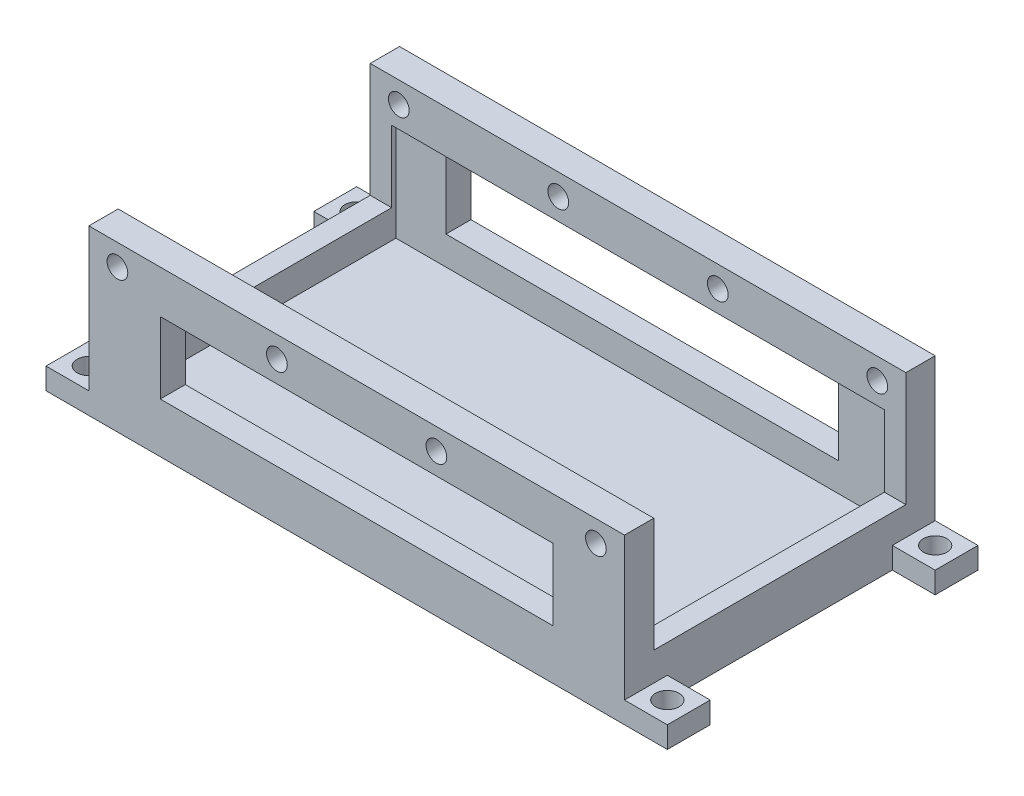
SolidWorks part; units mm, degrees
ref_plane "Front Plane" through (0, 0, 0) normal (0, 0, 1) x (1, 0, 0)
ref_plane "Top Plane" through (0, 0, 0) normal (0, 1, 0) x (1, 0, 0)
ref_plane "Right Plane" through (0, 0, 0) normal (1, 0, 0) x (0, 0, -1)
sketch "Sketch1" plane through (0, 0, 0) normal (0, 1, 0) x (1, 0, 0)
  line L0 (-34.5, -964.5) -> (-34.5, 49035.5) construction
  line L1 (0, 0) -> (-69, 0)
  line L2 (0, 0) -> (0, 35.5)
  line L3 (0, 35.5) -> (-69, 35.5)
  line L4 (-69, 0) -> (-69, 35.5)
  line L5 (-72, 39.5) -> (3, 39.5)
  line L6 (-72, 39.5) -> (-72, -4)
  line L7 (-72, -4) -> (3, -4)
  line L8 (3, 39.5) -> (3, -4)
  line L9 (-72, -4) -> (-78, -4)
  line L10 (-72, -4) -> (-72, 2)
  line L11 (-72, 2) -> (-78, 2)
  line L12 (-78, -4) -> (-78, 2)
  line L13 (-1071, 17.75) -> (48929, 17.75) construction
  line L14 (3, 2) -> (9, 2)
  line L15 (9, -4) -> (9, 2)
  line L16 (3, -4) -> (9, -4)
  line L17 (3, -4) -> (3, 2)
  line L18 (3, 39.5) -> (9, 39.5)
  line L19 (9, 39.5) -> (9, 33.5)
  line L20 (3, 33.5) -> (9, 33.5)
  line L21 (3, 39.5) -> (3, 33.5)
  line L22 (-72, 33.5) -> (-78, 33.5)
  line L23 (-78, 39.5) -> (-78, 33.5)
  line L24 (-72, 39.5) -> (-78, 39.5)
  line L25 (-72, 39.5) -> (-72, 33.5)
  circle A0 centre (-75, -1) radius 1.65
  circle A1 centre (6, -1) radius 1.65
  circle A2 centre (6, 36.5) radius 1.65
  circle A3 centre (-75, 36.5) radius 1.65
  point P15 (-75, 2)
  point P17 (-78, -1)
  point P21 (-34.5, 35.5)
  point P22 (-72, 17.75)
  dimension "D8" = 3.3
  dimension "D1" = 35.5
  dimension "D2" = 69
  dimension "D3" = 3
  dimension "D4" = 4
  dimension "D5" = 4
  dimension "D7" = 6
extrude "Boss-Extrude1" add sketch "Sketch1" along normal blind 3 contours L6 L24 L23 L22 A3 | L8 L5 L6 L7 L1 L4 L3 L2 | A0 | L8 L16 L15 L14 A1 | L8 L20 L19 L18 A2 | L9 L12 L11 L10 | L2 L1 L4 L3 region at (-34.5, 0, -38.633) region at (-72.0849, 0, -36.5) region at (6, 0, -39.4151) region at (6, 0, -1.9151) region at (-75, 0, 1)
sketch "Sketch2" plane through (0, 3, 0) normal (0, 1, 0) x (1, 0, 0)
  line L0 (3, 33.5) -> (3, 2) construction
  line L1 (-69, 36) -> (0, 36)
  line L2 (-69, 36) -> (-69, -0.5)
  line L3 (-69, -0.5) -> (0, -0.5)
  line L4 (0, 36) -> (0, -0.5)
  line L5 (-72, 33.5) -> (-72, 2) construction
  line L6 (9, 39.5) -> (-78, 39.5) construction
  line L7 (-78, -4) -> (9, -4) construction
  line L20 (-72, 33.5) -> (-72, 39.5)
  line L21 (-72, 2) -> (-72, -4)
  line L22 (3, 2) -> (3, -4)
  line L23 (3, 33.5) -> (3, 39.5)
  line L32 (-78, 33.5) -> (-72, 33.5)
  line L33 (-72, 33.5) -> (-72, 2)
  line L34 (-72, 2) -> (-78, 2)
  line L35 (-78, 2) -> (-78, -4)
  line L36 (-78, -4) -> (9, -4)
  line L37 (9, -4) -> (9, 2)
  line L38 (9, 2) -> (3, 2)
  line L39 (3, 2) -> (3, 33.5)
  line L40 (3, 33.5) -> (9, 33.5)
  line L41 (9, 33.5) -> (9, 39.5)
  line L42 (9, 39.5) -> (-78, 39.5)
  line L43 (-78, 39.5) -> (-78, 33.5)
  line L45 (-72, 33.5) -> (-72, 2)
  line L48 (-72, -4) -> (3, -4)
  line L49 (9, -4) -> (9, 2)
  line L51 (3, 2) -> (3, 33.5)
  line L53 (9, 33.5) -> (9, 39.5)
  line L54 (3, 39.5) -> (-72, 39.5)
  line M18 (-72, 33.5) -> (-72, 2)
  line M21 (-78, -4) -> (9, -4)
  line M24 (3, 2) -> (3, 33.5)
  line M27 (9, 39.5) -> (-78, 39.5)
  dimension "D1" = 3
  dimension "D2" = 3
  dimension "D3" = 3.5
  dimension "D4" = 3.5
  dimension "D6" = 36.5
  dimension "D7" = 69
  dimension "D5" = 0
extrude "Boss-Extrude2" add sketch "Sketch2" along normal blind 4 contours L23 L20 L21 L22 L1 L4 L3 L2 M24 M27 M18 M21 region at (-71.133, 3, -36.5)
sketch "Sketch3" plane through (0, 7, 0) normal (0, 1, 0) x (1, 0, 0)
  line L0 (0, 36) -> (0, -0.5) construction
  line L1 (-69, -0.5) -> (0, -0.5) construction
  line L2 (-69, 36) -> (-69, -0.5) construction
  line L3 (-69, 36) -> (0, 36) construction
  line L4 (3, -4) -> (3, 39.5)
  line L5 (3, 39.5) -> (-72, 39.5)
  line L6 (-72, 39.5) -> (-72, -4)
  line L7 (-72, -4) -> (3, -4)
  line L8 (3, -4) -> (3, 0.1)
  line L9 (3, 39.5) -> (-7, 39.5)
  line L10 (-72, 39.5) -> (-72, 35.4)
  line L11 (-72, -4) -> (-62, -4)
  line L12 (0, 36) -> (0, 35.4)
  line L13 (-69, -0.5) -> (-62, -0.5)
  line L14 (-69, 36) -> (-69, 35.4)
  line L15 (-69, 36) -> (-62, 36)
  line L16 (-69, 35.4) -> (-72, 35.4)
  line L17 (-62, 36) -> (-62, 39.5)
  line L18 (-34.5, -964.5) -> (-34.5, 49035.5) construction
  line L19 (-1071, 17.75) -> (48929, 17.75) construction
  line L20 (0, 35.4) -> (3, 35.4)
  line L21 (-7, 36) -> (-7, 39.5)
  line L22 (0, 0.1) -> (3, 0.1)
  line L23 (-7, -0.5) -> (-7, -4)
  line L24 (-62, -0.5) -> (-62, -4)
  line L25 (-69, 0.1) -> (-72, 0.1)
  line L26 (-72, 0.1) -> (-72, -4)
  line L27 (-69, 0.1) -> (-69, -0.5)
  line L28 (-7, -0.5) -> (0, -0.5)
  line L29 (-7, -4) -> (3, -4)
  line L30 (0, 0.1) -> (0, -0.5)
  line L31 (3, 35.4) -> (3, 39.5)
  line L32 (-7, 36) -> (0, 36)
  line L33 (-62, 39.5) -> (-72, 39.5)
  dimension "D2" = 10
  dimension "D3" = 4.1
  dimension "D1" = 0
extrude "Boss-Extrude3" add sketch "Sketch3" along normal blind 10
sketch "Sketch4" plane through (0, 17, 0) normal (0, 1, 0) x (1, 0, 0)
  line L1 (-72, 39.5) -> (3, 39.5)
  line L2 (-72, 39.5) -> (-72, 35.4)
  line L3 (-72, 35.4) -> (3, 35.4)
  line L4 (3, 39.5) -> (3, 35.4)
  line L5 (3, -4) -> (-72, -4)
  line L6 (3, -4) -> (3, 0.1)
  line L7 (3, 0.1) -> (-72, 0.1)
  line L8 (-72, -4) -> (-72, 0.1)
extrude "Boss-Extrude4" add sketch "Sketch4" along normal blind 6
sketch "Sketch5" plane through (0, 0, 4) normal (0, 0, 1) x (1, 0, 0)
  line L0 (-62, 17) -> (-62, 23) construction
  line L1 (-72, 23) -> (3, 23) construction
  line L2 (-72, 23) -> (-72, 3) construction
  line L3 (3, 23) -> (3, 3) construction
  circle A0 centre (-68, 20) radius 1.45
  circle A1 centre (-45.6667, 20) radius 1.45
  circle A2 centre (-23.3333, 20) radius 1.45
  circle A3 centre (-1, 20) radius 1.45
  point P8 (-62, 20)
  dimension "D1" = 2.9
  dimension "D2" = 4
  dimension "D4" = 4
  dimension "D3" = 4
extrude "Cut-Extrude1" cut sketch "Sketch5" against normal through all
